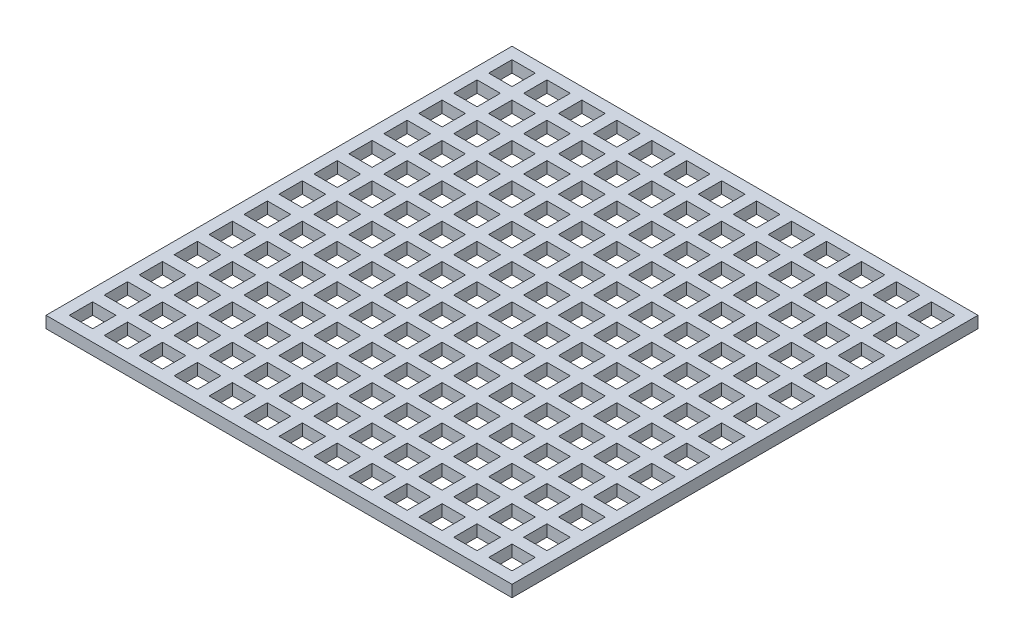
SolidWorks part; units mm, degrees
ref_plane "Front Plane" through (0, 0, 0) normal (0, 0, 1) x (1, 0, 0)
ref_plane "Top Plane" through (0, 0, 0) normal (0, 1, 0) x (1, 0, 0)
ref_plane "Right Plane" through (0, 0, 0) normal (1, 0, 0) x (0, 0, -1)
sketch "Sketch1" plane through (0, 0, 0) normal (0, 1, 0) x (1, 0, 0)
  line L1 (-25.4, 25.4) -> (25.4, 25.4)
  line L2 (-25.4, 25.4) -> (-25.4, -25.4)
  line L3 (-25.4, -25.4) -> (25.4, -25.4)
  line L4 (25.4, 25.4) -> (25.4, -25.4)
  line L5 (-25.4, 25.4) -> (25.4, -25.4) construction
  line L6 (-25.4, -25.4) -> (25.4, 25.4) construction
  point P0 (0, 0)
  dimension "D1" = 50.8
  dimension "D2" = 50.8
extrude "Boss-Extrude1" add sketch "Sketch1" along normal blind 1.27
sketch "Sketch4" plane through (0, 1.27, 0) normal (0, 1, 0) x (1, 0, 0)
  line L0 (-25.4, 25.4) -> (-25.4, -25.4) construction
  line L1 (-24.13, 24.13) -> (-21.59, 24.13)
  line L2 (-24.13, 24.13) -> (-24.13, 21.59)
  line L3 (-24.13, 21.59) -> (-21.59, 21.59)
  line L4 (-21.59, 24.13) -> (-21.59, 21.59)
  line L5 (-24.13, 24.13) -> (-21.59, 21.59) construction
  line L6 (-24.13, 21.59) -> (-21.59, 24.13) construction
  line L7 (25.4, 25.4) -> (-25.4, 25.4) construction
  point P0 (-22.86, 22.86)
  dimension "D1" = 2.54
  dimension "D2" = 2.54
  dimension "D3" = 2.54
  dimension "D4" = 2.54
extrude "Cut-Extrude2" cut sketch "Sketch4" against normal up to next
pattern_linear "LPattern3" count 13 spacing 3.81 along (1, 0, 0) count 13 spacing 3.81 along (0, 0, 1) of "Cut-Extrude2"
